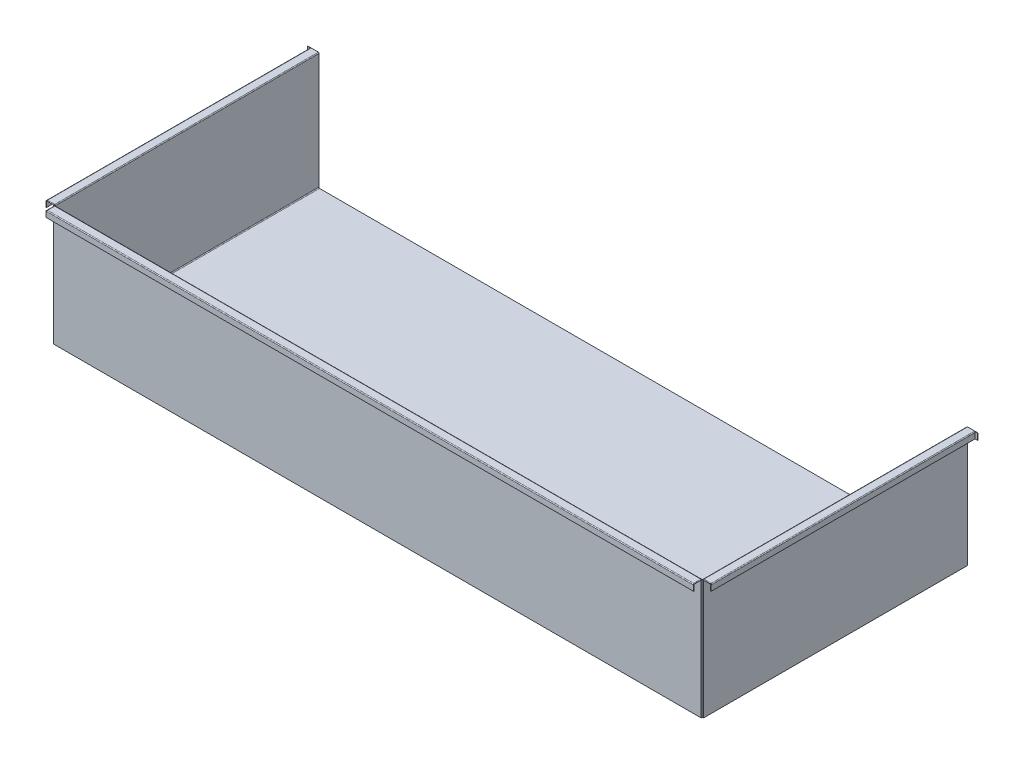
SolidWorks part; units mm, degrees
material "1023 Carbon Steel Sheet (SS)"
ref_plane "Front Plane" through (0, 0, 0) normal (0, 0, 1) x (1, 0, 0)
ref_plane "Top Plane" through (0, 0, 0) normal (0, 1, 0) x (1, 0, 0)
ref_plane "Right Plane" through (0, 0, 0) normal (1, 0, 0) x (0, 0, -1)
sketch "Sketch1" plane through (0, 0, 0) normal (0, 0, 1) x (1, 0, 0)
  line L0 (-412.75, 0) -> (412.75, 0)
  line L1 (412.75, 0) -> (412.75, 149.225)
  line L2 (412.75, 149.225) -> (423.8625, 149.225)
  line L3 (423.8625, 149.225) -> (423.8625, 141.2875)
  line L6 (423.3545, 148.717) -> (414.3375, 148.717)
  line L7 (414.3375, 148.717) -> (414.3375, -3.175)
  line L8 (414.3375, -3.175) -> (-414.3375, -3.175)
  line L10 (423.3545, 141.2875) -> (423.3545, 148.717)
  line L12 (423.8625, 141.2875) -> (423.3545, 141.2875)
  line L13 (0, 0) -> (0, 108.2341) construction
  line L14 (-423.8625, 141.2875) -> (-423.3545, 141.2875)
  line L15 (-423.3545, 141.2875) -> (-423.3545, 148.717)
  line L16 (-414.3375, 148.717) -> (-414.3375, -3.175)
  line L17 (-423.3545, 148.717) -> (-414.3375, 148.717)
  line L18 (-423.8625, 149.225) -> (-423.8625, 141.2875)
  line L19 (-412.75, 149.225) -> (-423.8625, 149.225)
  line L20 (-412.75, 0) -> (-412.75, 149.225)
  point P11 (0, -3.175)
  point P20 (0, 0)
  point P21 (0, 0)
  point P22 (0, 0)
  dimension "D1" = 3.175
  dimension "D2" = 1.5875
  dimension "D3" = 0.508
  dimension "D4" = 0.508
  dimension "D5" = 7.9375
  dimension "D6" = 11.1125
  dimension "D7" = 149.225
  dimension "D8" = 825.5
extrude "Boss-Extrude1" add sketch "Sketch1" along normal blind 336.55
sketch "Sketch2" plane through (0, 0, 0) normal (0, 0, -1) x (-1, 0, 0)
  line L0 (-412.75, 149.225) -> (-427.0375, 149.225)
  line L1 (-427.0375, 149.225) -> (-427.0375, 141.2875)
  line L2 (-427.0375, 141.2875) -> (-412.75, 141.2875)
  line L3 (-412.75, 149.225) -> (-412.75, 0) construction
  line L4 (-412.75, 141.2875) -> (-412.75, 149.225)
  line L5 (-423.3545, 141.2875) -> (-423.8625, 141.2875) construction
  line L6 (0, 0) -> (0, 106.4565) construction
  line L7 (-412.75, 0) -> (412.75, 0) construction
  line L8 (427.0375, 141.2875) -> (412.75, 141.2875)
  line L9 (427.0375, 149.225) -> (427.0375, 141.2875)
  line L10 (412.75, 149.225) -> (427.0375, 149.225)
  line L11 (412.75, 141.2875) -> (412.75, 149.225)
  dimension "D1" = 14.2875
extrude "Boss-Extrude2" add sketch "Sketch2" along normal blind 0.508
sketch "Sketch3" plane through (0, 0, 0) normal (1, 0, 0) x (0, 0, -1)
  line L0 (-336.55, -3.175) -> (-336.55, 149.225)
  line L1 (-336.55, 149.225) -> (-347.6625, 149.225)
  line L2 (-347.6625, 149.225) -> (-347.6625, 141.2875)
  line L3 (-347.6625, 141.2875) -> (-347.1545, 141.2875)
  line L4 (-347.1545, 141.2875) -> (-347.1545, 148.717)
  line L5 (-347.1545, 148.717) -> (-338.1375, 148.717)
  line L6 (-338.1375, 148.717) -> (-338.1375, -3.175)
  line L8 (-336.55, -3.175) -> (0, -3.175) construction
  line L10 (-336.55, 149.225) -> (0, 149.225) construction
  line L11 (-336.55, 141.2875) -> (-336.55, 149.225) construction
  line L12 (-338.1375, -3.175) -> (-336.55, -3.175)
  line L13 (-336.55, 149.225) -> (-336.55, 0) construction
  dimension "D1" = 0.508
  dimension "D2" = 0.508
  dimension "D3" = 1.5875
  dimension "D4" = 11.1125
extrude "Boss-Extrude6" add sketch "Sketch3" along normal mid plane 825.5254
fillet "Fillet1" radius 1.016 1 edges at (412.75, 74.6125, 336.55)
fillet "Fillet2" radius 1.016 1 edges at (412.7627, 73.025, 336.55)
fillet "Fillet3" radius 1.016 2 edges at (-412.75, 74.6125, 336.55) (-412.7627, 73.025, 336.55)
fillet "Fillet4" radius 1.016 5 edges at (-412.75, 0, 167.767) (-412.4524, 0, 336.2524) (0, 0, 336.55) (412.4524, 0, 336.2524) (412.75, 0, 167.767)
fillet "Fillet5" radius 1.016 14 edges at (418.8206, 149.225, 336.55) (413.0603, 149.225, 336.8476) (-418.8206, 149.225, 336.55) (-413.0603, 149.225, 336.8476) (-412.75, 149.225, 167.513) (-412.4524, 149.225, 336.2524) (0, 149.225, 336.55) (412.4524, 149.225, 336.2524) (412.7627, 149.225, 342.6143) (-412.7627, 149.225, 342.6143) (0, 149.225, 347.6625) (-423.8625, 149.225, 168.275) (412.75, 149.225, 167.513) (423.8625, 149.225, 168.275)
